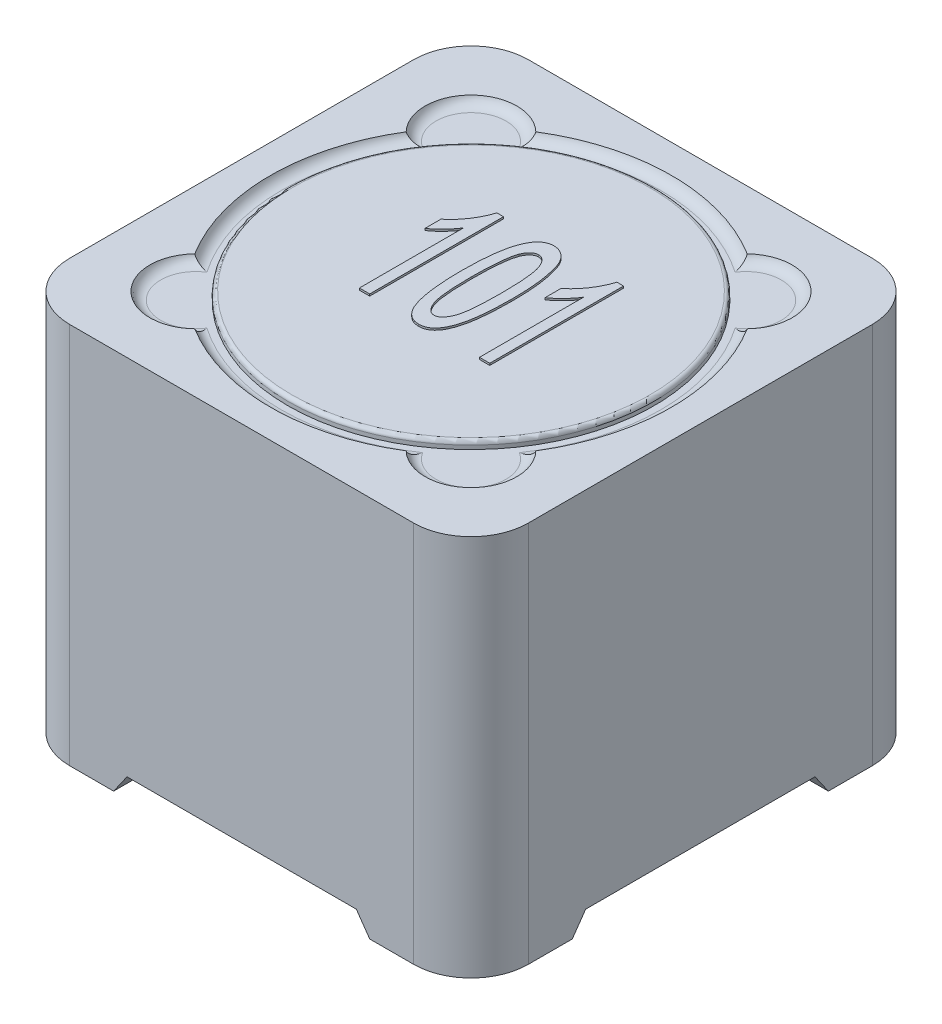
SolidWorks part; units mm, degrees
ref_plane "Plan de face" through (0, 0, 0) normal (0, 0, 1) x (1, 0, 0)
ref_plane "Plan de dessus" through (0, 0, 0) normal (0, 1, 0) x (1, 0, 0)
ref_plane "Plan de droite" through (0, 0, 0) normal (1, 0, 0) x (0, 0, -1)
sketch "Esquisse1" plane through (0, 0, 0) normal (0, 1, 0) x (1, 0, 0)
  line L1 (-4.5, 6) -> (4.5, 6)
  line L2 (-6, 4.5) -> (-6, -4.5)
  line L3 (-4.5, -6) -> (4.5, -6)
  line L4 (6, 4.5) -> (6, -4.5)
  line L5 (-6, 6) -> (6, -6) construction
  line L6 (-6, -6) -> (6, 6) construction
  arc A0 (-4.5, -6) -> (-6, -4.5) centre (-4.5, -4.5) cw
  arc A1 (6, -4.5) -> (4.5, -6) centre (4.5, -4.5) cw
  arc A2 (6, 4.5) -> (4.5, 6) centre (4.5, 4.5) ccw
  arc A3 (-4.5, 6) -> (-6, 4.5) centre (-4.5, 4.5) ccw
  point P0 (0, 0)
  dimension "D3" = 1.5
  dimension "D1" = 12
  dimension "D2" = 12
extrude "Boss.-Extru.1" add sketch "Esquisse1" along normal blind 10
sketch "Esquisse2" plane through (0, 10, 0) normal (0, 1, 0) x (1, 0, 0)
  line L0 (4.5, 6) -> (-4.5, 6) construction
  line L2 (-6, 4.5) -> (-6, -4.5) construction
  line L8 (-4.5, -6) -> (4.5, -6) construction
  line L9 (6, -4.5) -> (6, 4.5) construction
  arc A0 (-2.7657, 4.4625) -> (-4.4625, 2.7657) centre (-3.6, 3.6) ccw
  arc A1 (-4.4625, -2.7657) -> (-2.7657, -4.4625) centre (-3.6, -3.6) ccw
  arc A2 (2.7657, -4.4625) -> (4.4625, -2.7657) centre (3.6, -3.6) ccw
  arc A3 (4.4625, 2.7657) -> (2.7657, 4.4625) centre (3.6, 3.6) ccw
  arc A4 (-4.4625, 2.7657) -> (-4.4625, -2.7657) centre (0, 0) ccw
  arc A5 (2.7657, 4.4625) -> (-2.7657, 4.4625) centre (0, 0) ccw
  arc A6 (-2.7657, -4.4625) -> (2.7657, -4.4625) centre (0, 0) ccw
  arc A7 (4.4625, -2.7657) -> (4.4625, 2.7657) centre (0, 0) ccw
  dimension "D5" = 2.4
  dimension "D3" = 2.4
  dimension "D7" = 2.4
  dimension "D10" = 2.4
  dimension "D11" = 10.5
  dimension "D1" = 2.4
  dimension "D2" = 2.4
  dimension "D4" = 2.4
  dimension "D6" = 2.4
  dimension "D8" = 2.4
  dimension "D9" = 2.4
extrude "Enlèv. mat.-Extru.2" cut sketch "Esquisse2" against normal blind 0.2
sketch "Esquisse5" plane through (0, 9.8, 0) normal (0, 1, 0) x (1, 0, 0)
  circle A0 centre (0, 0) radius 4.7887
extrude "Boss.-Extru.4" add sketch "Esquisse5" along normal blind 0.2
fillet "Congé4" radius 0.1 1 edges at (0, 10, 4.7887)
fillet "Congé5" radius 0.3 8 edges at (5.25, 9.8, 0) (4.4485, 9.8, 4.4485) (0, 9.8, 5.25) (0, 9.8, -5.25) (4.4485, 9.8, -4.4485) (-4.4485, 9.8, 4.4485) (-5.25, 9.8, 0) (-4.4485, 9.8, -4.4485)
sketch "Esquisse6" plane through (0, 10, 0) normal (0, 1, 0) x (1, 0, 0)
  text T0 "101\r\n" font "Arial" height 3.5
sketch "Esquisse7" plane through (6, 0, 0) normal (1, 0, 0) x (0, 0, -1)
  line L0 (-3, 0.5) -> (3, 0.5)
  line L1 (3, 0.5) -> (3.35, 0)
  line L3 (-4.5, 0) -> (4.5, 0) construction
  line L4 (-3, 0.5) -> (-3.35, 0)
  line L5 (-3.35, 0) -> (3.35, 0)
  dimension "D1" = 3
  dimension "D2" = 3
  dimension "D3" = 0.35
  dimension "D4" = 0.35
  dimension "D5" = 0.5
extrude "Enlèv. mat.-Extru.4" cut sketch "Esquisse7" against normal through all
sketch "Esquisse8" plane through (0, 0, 6) normal (0, 0, 1) x (1, 0, 0)
  line L0 (-3, 0.5) -> (3, 0.5)
  line L1 (-4.5, 0) -> (4.5, 0) construction
  line L2 (3, 0.5) -> (3.35, 0)
  line L3 (-3, 0.5) -> (-3.35, 0)
  line L4 (-3.35, 0) -> (3.35, 0)
  dimension "D1" = 0.5
  dimension "D2" = 3
  dimension "D3" = 3
  dimension "D4" = 0.35
  dimension "D5" = 0.35
extrude "Enlèv. mat.-Extru.5" cut sketch "Esquisse8" against normal through all
sketch "Esboço3" plane through (0, 10, 0) normal (0, 1, 0) x (1, 0, 0)
extrude "Ressalto-extrusão1" add sketch "Esquisse6" along normal blind 0.05
